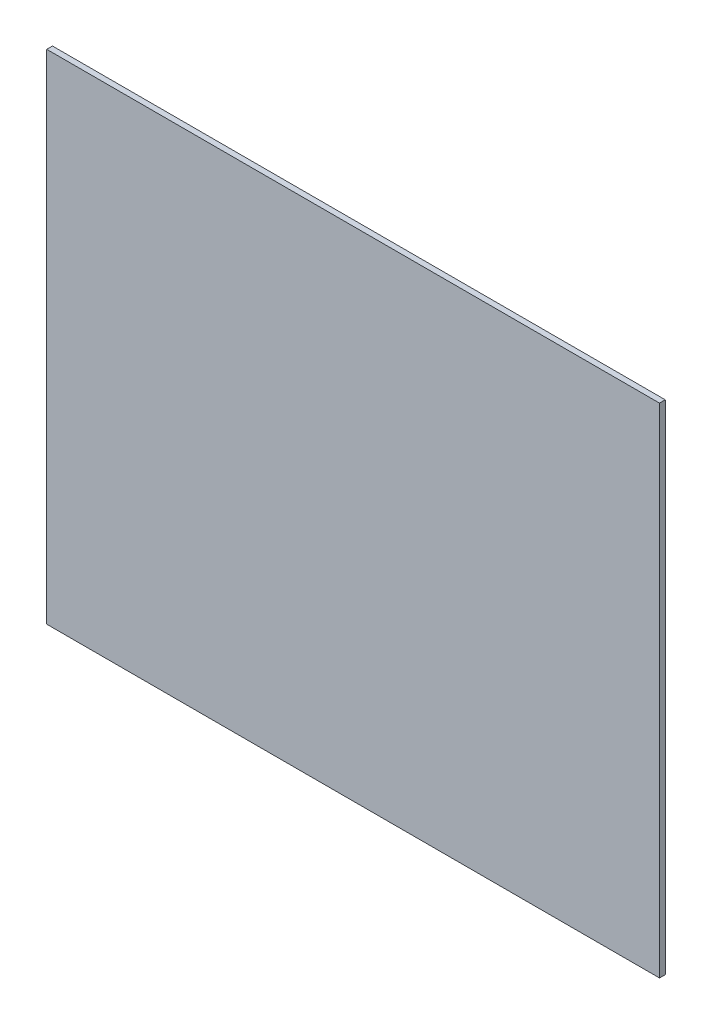
SolidWorks part; units mm, degrees
ref_plane "Спереди" through (0, 0, 0) normal (0, 0, 1) x (1, 0, 0)
ref_plane "Сверху" through (0, 0, 0) normal (0, 1, 0) x (1, 0, 0)
ref_plane "Справа" through (0, 0, 0) normal (1, 0, 0) x (0, 0, -1)
other "Configuration Table"
sketch "Эскиз1" plane through (0, 0, 0) normal (0, 0, 1) x (1, 0, 0)
  line L1 (160, 130) -> (-160, 130)
  line L2 (160, 130) -> (160, -130)
  line L3 (160, -130) -> (-160, -130)
  line L4 (-160, 130) -> (-160, -130)
  line L5 (160, 130) -> (-160, -130) construction
  line L6 (160, -130) -> (-160, 130) construction
  point P0 (0, 0)
  dimension "D1" = 260
  dimension "D2" = 320
extrude "Бобышка-Вытянуть1" add sketch "Эскиз1" along normal blind 3
